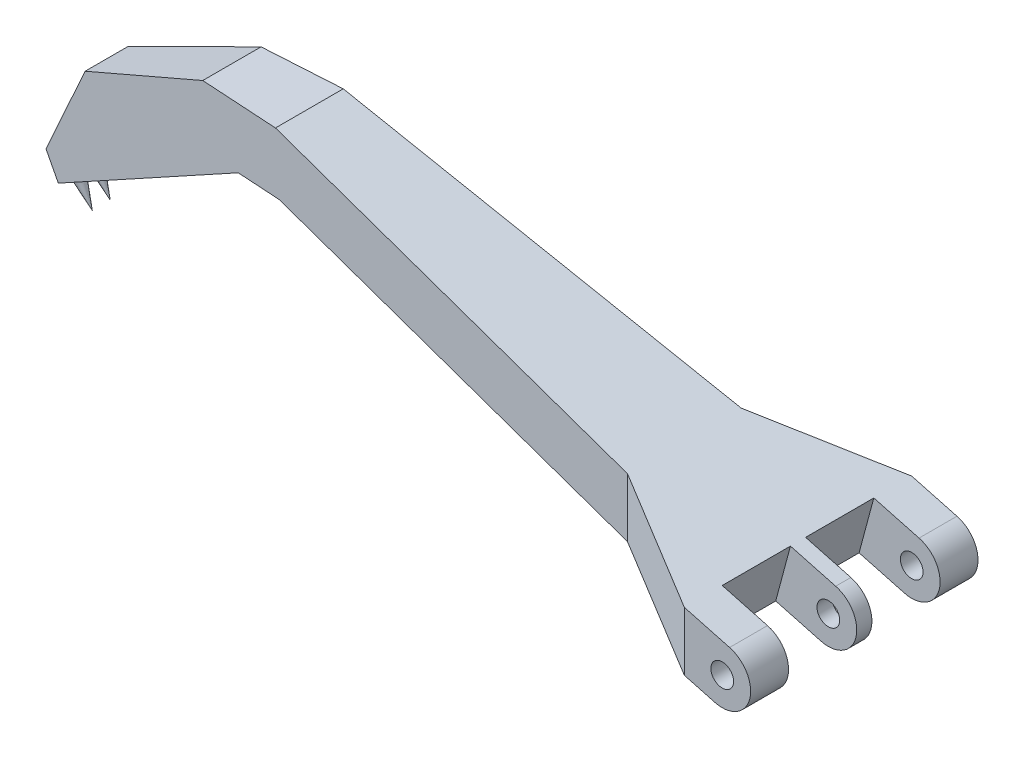
SolidWorks part; units mm, degrees
material "ABS"
ref_plane "Front Plane" through (0, 0, 0) normal (0, 0, 1) x (1, 0, 0)
ref_plane "Top Plane" through (0, 0, 0) normal (0, 1, 0) x (1, 0, 0)
ref_plane "Right Plane" through (0, 0, 0) normal (1, 0, 0) x (0, 0, -1)
sketch "Sketch3" plane through (0, 0, 0) normal (0, 0, 1) x (1, 0, 0)
  line L0 (0.9706, 3.6222) -> (-69.4823, 22.5)
  line L1 (-69.4823, 22.5) -> (-79.7011, 22.5)
  line L2 (-79.7011, 22.5) -> (-96.234, 14.7906)
  line L3 (-96.234, 14.7906) -> (-101.7321, 3)
  line L4 (-101.7321, 3) -> (-100, 0)
  line L5 (-100, 0) -> (-74.715, 14.5983)
  line L6 (-74.715, 14.5983) -> (-68.9706, 14.5983)
  line L7 (-68.9706, 14.5983) -> (-0.9706, -3.6222)
  line L8 (-0.9706, -3.6222) -> (0.9706, 3.6222) construction
  line L9 (-5.6356, -2.3722) -> (-3.6945, 4.8722) construction
  line L10 (-100, 0) -> (0, 0) construction
  circle A0 centre (0, 0) radius 1.5
  arc A2 (-0.9706, -3.6222) -> (0.9706, 3.6222) centre (0, 0) ccw
  point P14 (-5, 0)
  dimension "D2" = 3
  dimension "D1" = 100
  dimension "D3" = 7.5
  dimension "D4" = 68
  dimension "D5" = 30
  dimension "D6" = 15
  dimension "D7" = 125
  dimension "D8" = 5.498
  dimension "D9" = 3
  dimension "D10" = 155
  dimension "D11" = 22.5
sketch "Sketch4" plane through (0, 0, 0) normal (1, 0, 0) x (0, 0, -1)
  line L0 (-15, 0) -> (15, 0)
  point P4 (0, 0)
  dimension "D1" = 30
ref_plane "Plane1" through (-101.7321, 0, 0) normal (1, 0, 0) x (0, 0, -1)
sketch "Sketch5" plane through (-101.7321, 0, 0) normal (1, 0, 0) x (0, 0, -1)
  line L0 (2.5, 0) -> (-2.5, 0)
  point P4 (0, 0)
  dimension "D1" = 5
sketch "Sketch14" plane through (0, 0, 0) normal (0, 0, 1) x (1, 0, 0)
  line L0 (-153.9208, -162.5929) -> (-22.7793, -162.5929) construction
extrude "Boss-Extrude2" add sketch "Sketch3" along direction (0, 0, -1) on the side against the normal up to vertex (15 mm away) and the other way up to vertex (15 mm away) up to point (0, 0, -15) other way up to point (0, 0, 15)
sketch "Sketch12" plane through (0, 0, 0) normal (0, 1, 0) x (1, 0, 0)
  line L0 (-101.7321, 2.5) -> (-101.7321, -2.5) construction
  line L1 (-101.7321, 2.5) -> (-5, 2.5) construction
  line L2 (-101.7321, 2.5) -> (-101.7321, -2.5)
  line L3 (-5, -15) -> (-5, 15)
  line L4 (-101.7321, 2.5) -> (-5, 15) construction
  line L5 (-101.7321, -2.5) -> (-5, -15) construction
  line L6 (-101.7321, 0) -> (0, 0) construction
  line L7 (0, -15) -> (0, 15) construction
  line L8 (0, -15) -> (0, 15) construction
  line L9 (-101.7321, 2.5) -> (-20, 7.5)
  line L10 (-20, 7.5) -> (-5, 15)
  line L11 (-20, -7.5) -> (-5, -15)
  line L12 (-101.7321, -2.5) -> (-20, -7.5)
  dimension "D1" = 5
  dimension "D2" = 7.5
  dimension "D3" = 15
extrude "Cut-Extrude2" cut sketch "Sketch12" along normal through all and the other way through all flip side to cut contours L2 L12 L11 L3 L10 L9 | L3 L10 L9 L2 L12 L11 region at (-41.6669, 0, 0)
sketch "Sketch13" plane through (0, 0, 0) normal (0, 0, 1) x (1, 0, 0)
  line L0 (-5, 5.222) -> (-5, -2.5425) construction
  line L1 (-5, 5.222) -> (-5, -2.5425)
  line L8 (0.9706, 3.6222) -> (-5, 5.222)
  line L9 (-0.9706, -3.6222) -> (-5, -2.5425)
  arc A0 (-0.9706, -3.6222) -> (0.9706, 3.6222) centre (0, 0) ccw construction
  circle A1 centre (0, 0) radius 1.5 construction
  arc A2 (-0.9706, -3.6222) -> (0.9706, 3.6222) centre (0, 0) ccw
  circle A3 centre (0, 0) radius 1.5
extrude "Boss-Extrude3" add sketch "Sketch13" along direction (0, 0, 1) on the side of the normal up to vertex (15 mm away) and the other way up to vertex (15 mm away) up to point (-5, 5.222, 15) other way up to point (-5, 5.222, -15)
sketch "Sketch16" plane through (0.9706, 3.6222, 0) normal (0.2588, 0.9659, 0) x (0.9659, -0.2588, 0)
  line L0 (3.75, -15) -> (3.75, 15) construction
  line L1 (3.75, -15) -> (3.75, 15) construction
  line L2 (3.75, 15) -> (0, 15) construction
  line L3 (0, -15) -> (3.75, -15) construction
  line L4 (3.75, 15) -> (0, 15) construction
  line L5 (0, -15) -> (3.75, -15) construction
  line L6 (0, 15) -> (-6.1812, 15) construction
  line L7 (0, -15) -> (-6.1812, -15) construction
  line L8 (0, 15) -> (-6.1812, 15) construction
  line L9 (0, -15) -> (-6.1812, -15) construction
  line L10 (-6.1812, -15) -> (-6.1812, 15) construction
  line L11 (3.75, 0) -> (-6.1812, 0) construction
  line L12 (3.75, -1) -> (-6.1812, -1)
  line L13 (-6.1812, 1) -> (3.75, 1)
  line L14 (-6.1812, -10) -> (3.75, -10)
  line L15 (-6.1812, 10) -> (3.75, 10)
  line L16 (3.75, -10) -> (-6.1812, -10)
  line L17 (-6.1812, -10) -> (-6.1812, -1)
  line L18 (3.75, -1) -> (3.75, -10)
  line L19 (-6.1812, 10) -> (-6.1812, 1)
  line L20 (3.75, 1) -> (3.75, 10)
  line L21 (3.75, -1) -> (3.75, -10)
  line L22 (-6.1812, -10) -> (-6.1812, -1)
  line M12 (0, -15) -> (0, 15)
  dimension "D1" = 2
  dimension "D2" = 9
extrude "Cut-Extrude8" cut sketch "Sketch16" against normal up to surface (7.5 mm away) contours L15 L19 L13 M12 | L17 L14 L12 M12 | L18 L12 L14 M12 | L13 L20 L15 M12 region at (2.7817, 3.1369, 5.5) region at (-2.0147, 4.4221, -5.5) region at (2.7817, 3.1369, -5.5) region at (-2.0147, 4.4221, 5.5) up to face at (-23.7353, 2.4776, 0)
sketch "Sketch17" plane through (-25, 43.3013, 0) normal (0.5, -0.866, 0) x (0.866, 0.5, 0)
  line L0 (-86.6025, 0) -> (-57.4059, 0) construction
  line L1 (-86.6025, -2.606) -> (-86.6025, 2.606) construction
  line L2 (-57.4059, -4.1528) -> (-57.4059, 4.1528) construction
  line L3 (-86.6025, 2.606) -> (-57.4059, 4.1528) construction
  circle A0 centre (-85.1025, 1.1833) radius 0.75
  circle A1 centre (-85.1025, -1.1833) radius 0.75
  dimension "D1" = 1.5
  dimension "D2" = 1.5
  dimension "D3" = 1.5
extrude "Boss-Extrude4" add sketch "Sketch17" along normal blind 6 draft 12
